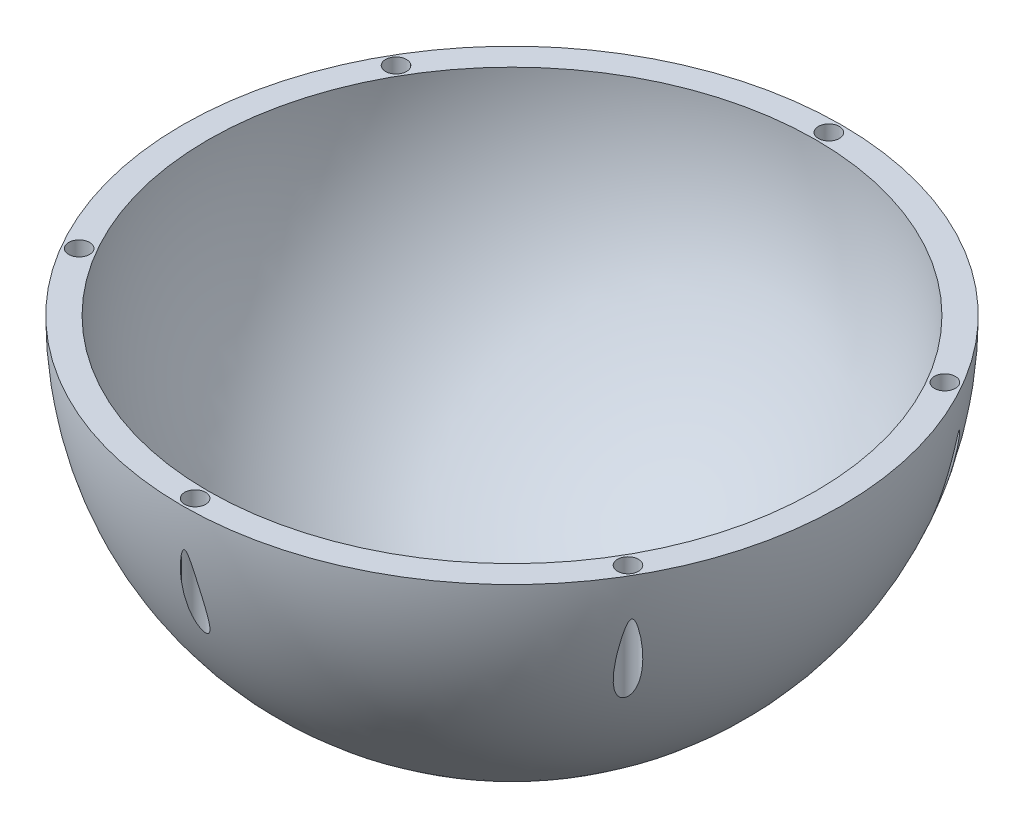
SolidWorks part; units mm, degrees
ref_plane "Front Plane" through (0, 0, 0) normal (0, 0, 1) x (1, 0, 0)
ref_plane "Top Plane" through (0, 0, 0) normal (0, 1, 0) x (1, 0, 0)
ref_plane "Right Plane" through (0, 0, 0) normal (1, 0, 0) x (0, 0, -1)
sketch "Sketch1" plane through (0, 0, 0) normal (0, 0, 1) x (1, 0, 0)
  line L0 (-123.952, 0) -> (-114.3, 0)
  line L1 (114.3, 0) -> (123.952, 0)
  line L2 (0, 0) -> (0, -142.9847) construction
  arc A0 (-114.3, 0) -> (114.3, 0) centre (0, 0) ccw
  arc A1 (-123.952, 0) -> (123.952, 0) centre (0, 0) ccw
  dimension "D1" = 9.652
revolve "Revolve1" add sketch "Sketch1" angle 360 about L2 region at (-119.126, -1.7529, 0)
sketch "Sketch2" plane through (0, 0, 0) normal (0, 1, 0) x (1, 0, 0)
  circle A0 centre (0, 0) radius 119.126 construction
  circle A2 centre (0, 119.126) radius 3.937
  circle A3 centre (103.1661, 59.563) radius 3.937
  circle A4 centre (103.1661, -59.563) radius 3.937
  circle A5 centre (0, -119.126) radius 3.937
  circle A6 centre (-103.1661, -59.563) radius 3.937
  circle A7 centre (-103.1661, 59.563) radius 3.937
  circle A8 centre (0, 0) radius 114.3 construction
  point P19 (0, 0)
  dimension "D1" = 4.826
  dimension "D3" = 7.874
  dimension "D2" = 6
extrude "Cut-Extrude1" cut sketch "Sketch2" against normal through all
sketch "Sketch3" plane through (0, 0, 0) normal (0, 1, 0) x (1, 0, 0)
  circle A0 centre (0, 119.126) radius 3.937
  circle A1 centre (103.2721, 59.6242) radius 3.937
  circle A2 centre (103.3781, -59.563) radius 3.937
  circle A3 centre (0.2119, -119.2484) radius 3.937
  circle A4 centre (-103.0602, -59.7465) radius 3.937
  circle A5 centre (-103.1661, 59.4406) radius 3.937
  circle A6 centre (0, 119.126) radius 1.397
  circle A7 centre (103.2721, 59.6242) radius 1.397
  circle A8 centre (103.3781, -59.563) radius 1.397
  circle A9 centre (0.2119, -119.2484) radius 1.397
  circle A10 centre (-103.0602, -59.7465) radius 1.397
  circle A11 centre (-103.1661, 59.4406) radius 1.397
  circle A12 centre (0, 0) radius 119.126
  point P16 (0.106, -0.0612)
  point P28 (0.106, -0.0612)
  dimension "D3" = 2.794
  dimension "D1" = 6
  dimension "D2" = 6
extrude "Boss-Extrude1" add sketch "Sketch3" against normal blind 2.54 rebuild error yes
